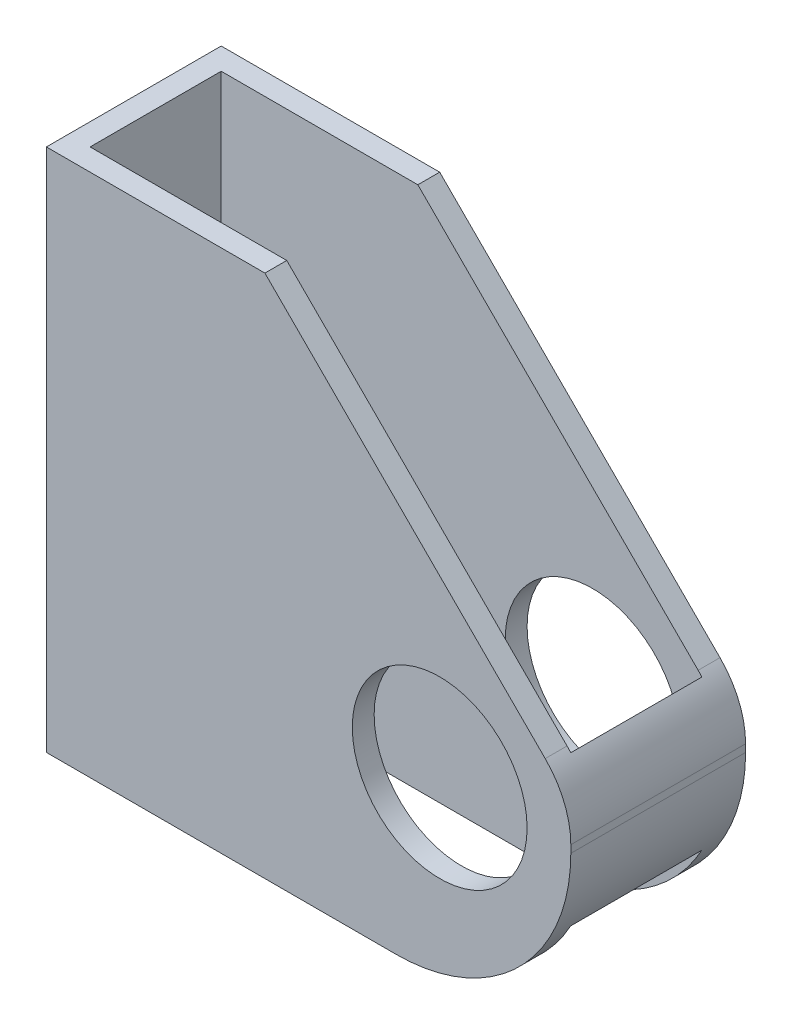
SolidWorks part; units mm, degrees
ref_plane "Front Plane" through (0, 0, 0) normal (0, 0, 1) x (1, 0, 0)
ref_plane "Top Plane" through (0, 0, 0) normal (0, 1, 0) x (1, 0, 0)
ref_plane "Right Plane" through (0, 0, 0) normal (1, 0, 0) x (0, 0, -1)
sketch "Sketch1" plane through (0, 0, 0) normal (0, 0, 1) x (1, 0, 0)
  line L1 (-38.1, 38.1) -> (38.1, 38.1)
  line L2 (-38.1, 38.1) -> (-38.1, -38.1)
  line L3 (-38.1, -38.1) -> (38.1, -38.1)
  line L4 (38.1, 38.1) -> (38.1, -38.1)
  line L5 (-38.1, 38.1) -> (38.1, -38.1) construction
  line L6 (-38.1, -38.1) -> (38.1, 38.1) construction
  circle A0 centre (19.05, -12.7) radius 12.7
  point P0 (0, 0)
  dimension "D3" = 57.15
  dimension "D4" = 25.4
  dimension "D5" = 25.4
  dimension "D1" = 76.2
  dimension "D2" = 76.2
extrude "Boss-Extrude1" add sketch "Sketch1" along normal mid plane 25.4
chamfer "Chamfer1" distance 44.45 angle 45 1 edges at (38.1, 38.1, 0)
fillet "Fillet1" radius 25.4 1 edges at (38.1, -38.1, 0)
fillet "Fillet2" radius 12.7 1 edges at (38.1, -6.35, 0)
sketch "Sketch3" plane through (0, -38.1, 0) normal (0, -1, 0) x (1, 0, 0)
  line L27 (-34.925, 9.525) -> (-34.925, -9.525)
  line L28 (-34.925, -9.525) -> (12.7, -9.525)
  line L29 (12.7, -9.525) -> (34.925, -9.525)
  line L30 (34.925, -9.525) -> (34.925, 9.525)
  line L31 (34.925, 9.525) -> (12.7, 9.525)
  line L32 (12.7, 9.525) -> (-34.925, 9.525)
  line L33 (-34.925, 9.525) -> (-34.925, -9.525)
  line L34 (-34.925, -9.525) -> (12.7, -9.525)
  line L35 (12.7, -9.525) -> (34.925, -9.525)
  line L36 (34.925, -9.525) -> (34.925, 9.525)
  line L37 (34.925, 9.525) -> (12.7, 9.525)
  line L38 (12.7, 9.525) -> (-34.925, 9.525)
  dimension "D1" = 3.175
extrude "Cut-Extrude2" cut sketch "Sketch3" against normal through all
hole_wizard "1/4 (0.25) Diameter Hole1" positions "Sketch5" profile "Sketch6" hole size "1/4" standard "ANSI Inch"
sketch "Sketch5" plane through (-38.1, 0, 0) normal (-1, 0, 0) x (0, 0, 1)
  point P0 (0, 19.05)
  point P2 (0, -19.05)
  dimension "D1" = 19.05
  dimension "D2" = 19.05
sketch "Sketch6" plane through (-38.1, 19.05, 0) normal (0, 1, 0) x (0, 0, 1)
  line L0 (0, 0) -> (0, 6.9877)
  line L1 (0, 6.9877) -> (3.175, 5.08)
  line L2 (3.175, 5.08) -> (3.175, 0)
  line L5 (3.175, 0) -> (0, 0)
  line L10 (0, 6.9877) -> (-3.175, 5.08) construction
  line L11 (0, -6.35) -> (0, 107.95) construction
  dimension "Hole Dia." = 6.35
  dimension "Hole Depth" = 5.08
  dimension "Drill Angle" = 118
